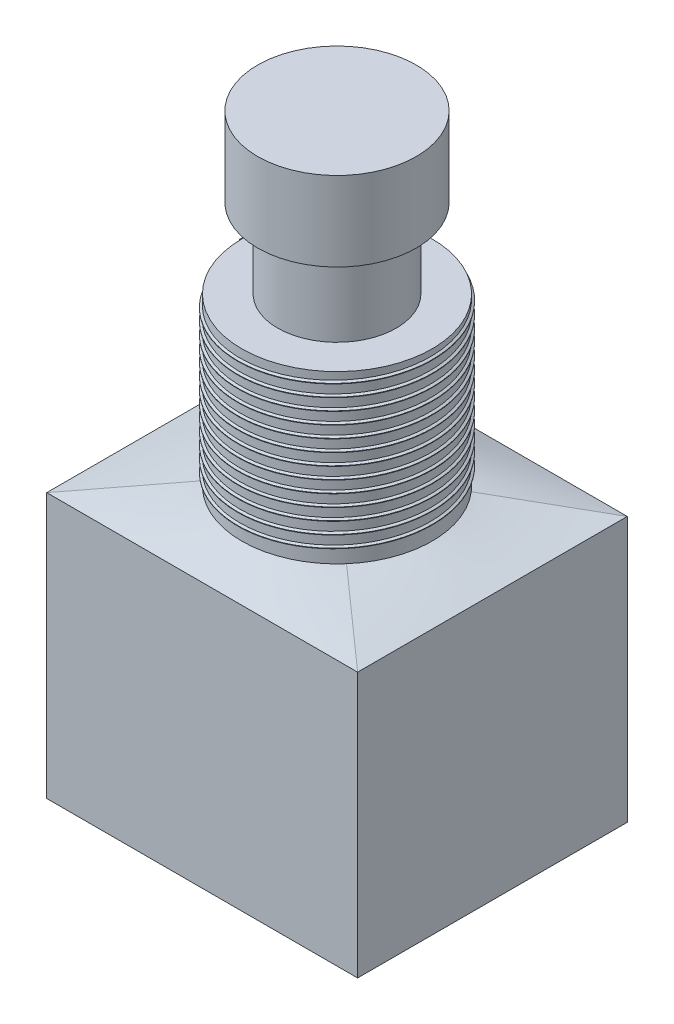
SolidWorks part; units mm, degrees
ref_plane "Front Plane" through (0, 0, 0) normal (0, 0, 1) x (1, 0, 0)
ref_plane "Top Plane" through (0, 0, 0) normal (0, 1, 0) x (1, 0, 0)
ref_plane "Right Plane" through (0, 0, 0) normal (1, 0, 0) x (0, 0, -1)
sketch "Sketch1" plane through (0, 0, 0) normal (0, 1, 0) x (1, 0, 0)
  line L1 (9.8, -8.5) -> (-9.8, -8.5)
  line L2 (9.8, -8.5) -> (9.8, 8.5)
  line L3 (9.8, 8.5) -> (-9.8, 8.5)
  line L4 (-9.8, -8.5) -> (-9.8, 8.5)
  line L5 (9.8, -8.5) -> (-9.8, 8.5) construction
  line L6 (9.8, 8.5) -> (-9.8, -8.5) construction
  point P0 (0, 0)
  dimension "D1" = 17
  dimension "D2" = 19.6
extrude "Base" add sketch "Sketch1" along normal blind 15.5 and the other way blind 1.2 contours L4 L3 L2 L1
sketch "Sketch3" plane through (0, 15.5, 0) normal (0, 1, 0) x (1, 0, 0)
  circle A0 centre (0, 0) radius 6
  dimension "D1" = 12
extrude "Boss-Extrude3" add sketch "Sketch3" along normal blind 1
sketch "Sketch11" plane through (0, 16.5, 0) normal (0, 1, 0) x (1, 0, 0)
  circle A0 centre (0, 0) radius 6
sketch "Sketch7" plane through (0, 16.5, 0) normal (0, 1, 0) x (1, 0, 0)
  circle A0 centre (0, 0) radius 6
  dimension "D1" = 12
extrude "Thread" add sketch "Sketch7" along normal blind 10.5
sketch "Sketch8" plane through (0, 27, 0) normal (0, 1, 0) x (1, 0, 0)
  circle A0 centre (0, 0) radius 3.7403
extrude "Shaft" add sketch "Sketch8" along normal blind 5
sketch "Sketch9" plane through (0, 32, 0) normal (0, 1, 0) x (1, 0, 0)
  circle A0 centre (0, 0) radius 5
extrude "Button" add sketch "Sketch9" along normal blind 5
sketch "Sketch10" plane through (0, 15.5, 0) normal (0, 1, 0) x (1, 0, 0)
  line L1 (9.8, -8.5) -> (-9.8, -8.5)
  line L2 (9.8, -8.5) -> (9.8, 8.5)
  line L3 (9.8, 8.5) -> (-9.8, 8.5)
  line L4 (-9.8, -8.5) -> (-9.8, 8.5)
  line L5 (9.8, -8.5) -> (-9.8, 8.5) construction
  line L6 (9.8, 8.5) -> (-9.8, -8.5) construction
  point P0 (0, 0)
loft "Loft1" add profiles "Sketch11", "Sketch10" connector at (0, 16.5, 6) connector at (-9.8, 15.5, 8.5)
thread "Thread1" pitch 0.25 method extrude profile "Thread Profile1" start angle 0, offset 0, length 10, pitch 0.75, diameter 12
ref_plane "Plane1" through (-6, 27, 0) normal (0, 0, 1) x (-1, 0, 0)
sketch "Thread Profile1" plane through (-6, 27, 0) normal (0, 0, 1) x (-1, 0, 0)
  line L0 (0, 0) -> (0, 0.25) construction
  line L1 (0, 0) -> (0.1353, 0.0781)
  line L2 (0.1353, 0.0781) -> (0.1353, 0.1094)
  line L3 (0.1353, 0.1094) -> (0, 0.1875)
  line L4 (0.1353, 0.0937) -> (0, 0.0937) construction
  line L11 (0, 0) -> (0, 0.1875)
  point P2 (0, 0)
  dimension "Pitch" = 0.25
  dimension "Profile_Angle" = 60
  dimension "Profile_Land" = 0.0312
  dimension "Profile_Height" = 0.1353
sketch "Sketch16" plane through (0, -1.2, 0) normal (0, -1, 0) x (1, 0, 0)
  line L0 (-0.5, 5.175) -> (0.5, 5.175)
  line L1 (-5.8, 5.175) -> (-4.8, 5.175)
  line L2 (-5.8, 5.175) -> (-5.8, 4.425)
  line L3 (-5.8, 4.425) -> (-4.8, 4.425)
  line L4 (-4.8, 5.175) -> (-4.8, 4.425)
  line L5 (-5.8, 5.175) -> (-4.8, 4.425) construction
  line L6 (-5.8, 4.425) -> (-4.8, 5.175) construction
  line L7 (-0.5, 5.175) -> (-0.5, 4.425)
  line L8 (-0.5, 4.425) -> (0.5, 4.425)
  line L9 (0.5, 5.175) -> (0.5, 4.425)
  line L10 (-0.5, 4.425) -> (0.5, 5.175) construction
  line L11 (-0.5, 5.175) -> (0.5, 4.425) construction
  line L12 (4.8, 5.175) -> (5.8, 5.175)
  line L13 (4.8, 5.175) -> (4.8, 4.425)
  line L14 (4.8, 4.425) -> (5.8, 4.425)
  line L15 (5.8, 5.175) -> (5.8, 4.425)
  line L16 (4.8, 4.425) -> (5.8, 5.175) construction
  line L17 (4.8, 5.175) -> (5.8, 4.425) construction
  line L18 (-0.5, 0.375) -> (0.5, 0.375)
  line L19 (-0.5, 0.375) -> (-0.5, -0.375)
  line L20 (-0.5, -0.375) -> (0.5, -0.375)
  line L21 (0.5, 0.375) -> (0.5, -0.375)
  line L22 (-0.5, -0.375) -> (0.5, 0.375) construction
  line L23 (-0.5, 0.375) -> (0.5, -0.375) construction
  line L24 (4.8, 0.375) -> (5.8, 0.375)
  line L25 (4.8, 0.375) -> (4.8, -0.375)
  line L26 (4.8, -0.375) -> (5.8, -0.375)
  line L27 (5.8, 0.375) -> (5.8, -0.375)
  line L28 (4.8, -0.375) -> (5.8, 0.375) construction
  line L29 (4.8, 0.375) -> (5.8, -0.375) construction
  line L30 (-0.5, -4.425) -> (0.5, -4.425)
  line L31 (-0.5, -4.425) -> (-0.5, -5.175)
  line L32 (-0.5, -5.175) -> (0.5, -5.175)
  line L33 (0.5, -4.425) -> (0.5, -5.175)
  line L34 (-0.5, -5.175) -> (0.5, -4.425) construction
  line L35 (-0.5, -4.425) -> (0.5, -5.175) construction
  line L36 (4.8, -4.425) -> (5.8, -4.425)
  line L37 (4.8, -4.425) -> (4.8, -5.175)
  line L38 (4.8, -5.175) -> (5.8, -5.175)
  line L39 (5.8, -4.425) -> (5.8, -5.175)
  line L40 (4.8, -5.175) -> (5.8, -4.425) construction
  line L41 (4.8, -4.425) -> (5.8, -5.175) construction
  line L42 (-5.8, 0.375) -> (-4.8, 0.375)
  line L43 (-5.8, 0.375) -> (-5.8, -0.375)
  line L44 (-5.8, -0.375) -> (-4.8, -0.375)
  line L45 (-4.8, 0.375) -> (-4.8, -0.375)
  line L46 (-5.8, -0.375) -> (-4.8, 0.375) construction
  line L47 (-5.8, 0.375) -> (-4.8, -0.375) construction
  line L48 (-5.8, -4.425) -> (-4.8, -4.425)
  line L49 (-5.8, -4.425) -> (-5.8, -5.175)
  line L50 (-5.8, -5.175) -> (-4.8, -5.175)
  line L51 (-4.8, -4.425) -> (-4.8, -5.175)
  line L52 (-5.8, -5.175) -> (-4.8, -4.425) construction
  line L53 (-5.8, -4.425) -> (-4.8, -5.175) construction
  line L54 (-5.3, 4.8) -> (0, 4.8) construction
  line L55 (-5.3, 4.8) -> (-5.3, 0) construction
  point P0 (-5.3, 4.8)
  point P7 (0, 4.8)
  point P12 (5.3, 4.8)
  point P17 (0, 0)
  point P22 (5.3, 0)
  point P27 (0, -4.8)
  point P32 (5.3, -4.8)
  point P37 (-5.3, 0)
  point P42 (-5.3, -4.8)
  dimension "D3" = 1
  dimension "D4" = 0.75
  dimension "D5" = 4.8
  dimension "D6" = 5.3
  dimension "D1" = 3
  dimension "D2" = 3
extrude "Pins" add sketch "Sketch16" along normal blind 3
equation "\"D2@Base\"=16.7-15.5"
